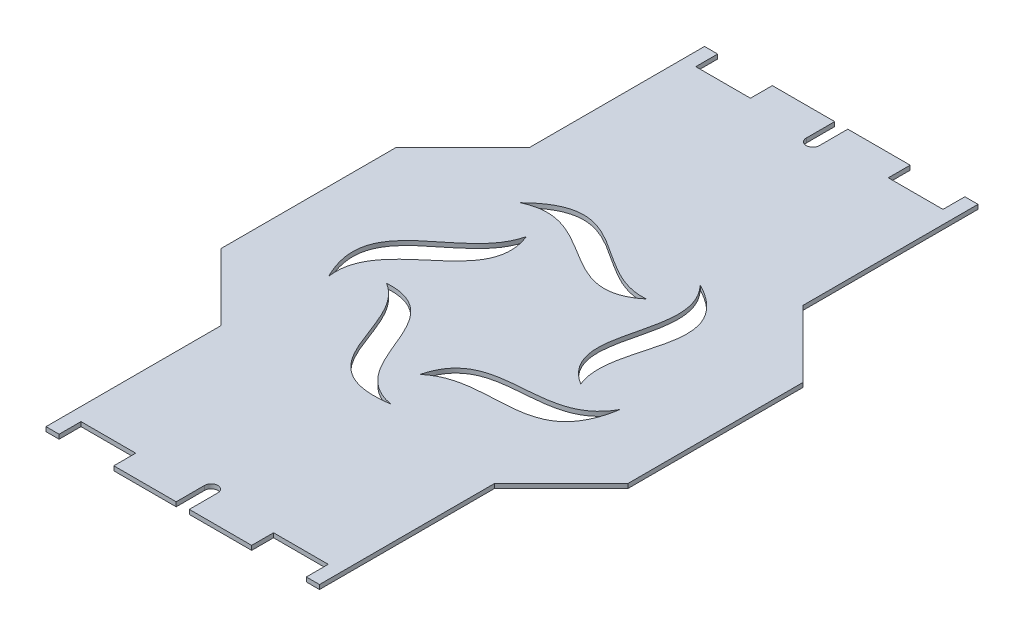
SolidWorks part; units mm, degrees
ref_plane "Front Plane" through (0, 0, 0) normal (0, 0, 1) x (1, 0, 0)
ref_plane "Top Plane" through (0, 0, 0) normal (0, 1, 0) x (1, 0, 0)
ref_plane "Right Plane" through (0, 0, 0) normal (1, 0, 0) x (0, 0, -1)
sketch "Sketch1" plane through (0, 0, 0) normal (0, 1, 0) x (1, 0, 0)
  line L0 (0, 0) -> (0, 150.5) construction
  line L1 (62.5, 150.5) -> (-62.5, 150.5)
  line L2 (-62.5, 150.5) -> (-62.5, 70.5)
  line L3 (-62.5, 70.5) -> (-93, 40)
  line L4 (-93, 40) -> (-93, -40)
  line L5 (0, 0) -> (-93, 0) construction
  line L6 (-62.5, -70.5) -> (-93, -40)
  line L7 (-62.5, -150.5) -> (-62.5, -70.5)
  line L8 (62.5, -150.5) -> (-62.5, -150.5)
  line L9 (62.5, -150.5) -> (62.5, -70.5)
  line L10 (62.5, -70.5) -> (93, -40)
  line L11 (93, 40) -> (93, -40)
  line L12 (62.5, 70.5) -> (93, 40)
  line L13 (62.5, 150.5) -> (62.5, 70.5)
  point P11 (0, -150.5)
  dimension "D1" = 80
  dimension "D2" = 40
extrude "Boss-Extrude1" add sketch "Sketch1" along normal blind 2
sketch "Sketch2" plane through (0, 2, 0) normal (0, 1, 0) x (1, 0, 0)
  line L0 (0, 0) -> (93, 0) construction
  line L1 (93, -40) -> (93, 40) construction
  line L2 (93, 0) -> (0, 0) construction
  line L3 (0, -150.5) -> (0, 150.5) construction
  line L4 (62.5, 150.5) -> (-62.5, 150.5) construction
  line L5 (-3, 150.5) -> (-3, 137.5)
  line L6 (3, 137.5) -> (3, 150.5)
  line L7 (3, 150.5) -> (-3, 150.5)
  line L8 (-3, 137.5) -> (-3, 150.5)
  line L9 (3, 150.5) -> (3, 137.5)
  line L10 (3, -150.5) -> (3, -137.5)
  line L11 (-3, -137.5) -> (-3, -150.5)
  line L12 (3, -150.5) -> (-3, -150.5)
  line L13 (3, -137.5) -> (3, -150.5)
  line L14 (-3, -150.5) -> (-3, -137.5)
  arc A0 (-3, 137.5) -> (3, 137.5) centre (0, 137.5) ccw
  arc A1 (-3, -137.5) -> (3, -137.5) centre (0, -137.5) cw
  point P12 (0, 0)
  line M9 (-62.5, -150.5) -> (62.5, -150.5)
  line M15 (62.5, 150.5) -> (-62.5, 150.5)
  dimension "D2" = 3
  dimension "D1" = 13
extrude "Cut-Extrude1" cut sketch "Sketch2" against normal blind 10 contours L5 A0 L6 M15 | A1 L11 L10 M9 region at (0, 2, -142.8073) region at (0, 2, 142.8073)
sketch "Sketch3" plane through (0, 2, 0) normal (0, 1, 0) x (1, 0, 0)
  circle A0 centre (0, 0) radius 75 construction
  spline S0 degree 3 poles (61.9353, -12.4807) (48.1881, -37.7648) (10.1523, -13.9307) (2.3401, -44.3064) knots 0 0 0 0 1 1 1 1
  spline S1 degree 3 poles (61.9353, -12.4807) (55.7621, -50.4582) (21.338, -28.075) (2.3401, -44.3064) knots 0 0 0 0 1 1 1 1
  spline S2 degree 3 poles (7.2692, -62.7607) (-21.0256, -57.4996) (-10.1116, -13.9602) (-41.4147, -15.917) knots 0 0 0 0 1 1 1 1
  spline S3 degree 3 poles (7.2692, -62.7607) (-30.7571, -68.6253) (-20.1071, -28.9693) (-41.4147, -15.917) knots 0 0 0 0 1 1 1 1
  spline S4 degree 3 poles (-57.4427, -26.3076) (-61.1826, 2.2281) (-16.4016, 5.3028) (-27.9358, 34.4691) knots 0 0 0 0 1 1 1 1
  spline S5 degree 3 poles (-57.4427, -26.3076) (-74.771, 8.0454) (-33.7649, 10.171) (-27.9358, 34.4691) knots 0 0 0 0 1 1 1 1
  spline S6 degree 3 poles (-42.7708, 46.5017) (-16.7874, 58.8767) (-0.0251, 17.2375) (24.1494, 37.2201) knots 0 0 0 0 1 1 1 1
  spline S7 degree 3 poles (-42.7708, 46.5017) (-15.4539, 73.5976) (-0.7608, 35.2553) (24.1494, 37.2201) knots 0 0 0 0 1 1 1 1
  spline S8 degree 3 poles (31.0089, 55.0473) (50.8075, 34.1597) (16.3861, 5.3506) (42.861, -11.4658) knots 0 0 0 0 1 1 1 1
  spline S9 degree 3 poles (31.0089, 55.0473) (65.22, 37.4405) (33.2947, 11.618) (42.861, -11.4658) knots 0 0 0 0 1 1 1 1
  point P35 (0, 0)
  dimension "D1" = 150
extrude "Cut-Extrude2" cut sketch "Sketch3" against normal blind 10
sketch "Sketch4" plane through (0, 2, 0) normal (0, 1, 0) x (1, 0, 0)
  line L0 (0, -150.5) -> (0, 150.5) construction
  line L1 (0, 150.5) -> (0, -150.5) construction
  line L2 (0, 0) -> (93, 0) construction
  line L3 (93, -40) -> (93, 40) construction
  line L4 (62.5, 150.5) -> (3, 150.5) construction
  line L5 (0, 150.5) -> (44, 150.5)
  line L6 (-31.5, 160.5) -> (-31.5, 140.5)
  line L7 (56.5, 160.5) -> (31.5, 160.5)
  line L8 (56.5, 160.5) -> (56.5, 140.5)
  line L9 (56.5, 140.5) -> (31.5, 140.5)
  line L10 (31.5, 160.5) -> (31.5, 140.5)
  line L11 (56.5, 160.5) -> (31.5, 140.5) construction
  line L12 (56.5, 140.5) -> (31.5, 160.5) construction
  line L13 (-56.5, 160.5) -> (-31.5, 160.5)
  line L14 (-56.5, 160.5) -> (-56.5, 140.5)
  line L15 (-56.5, 140.5) -> (-31.5, 140.5)
  line L16 (56.5, -140.5) -> (31.5, -160.5) construction
  line L17 (56.5, -160.5) -> (31.5, -140.5) construction
  line L18 (-56.5, -140.5) -> (-31.5, -140.5)
  line L19 (-56.5, -160.5) -> (-56.5, -140.5)
  line L20 (-56.5, -160.5) -> (-31.5, -160.5)
  line L21 (31.5, -160.5) -> (31.5, -140.5)
  line L22 (56.5, -140.5) -> (31.5, -140.5)
  line L23 (56.5, -160.5) -> (56.5, -140.5)
  line L24 (56.5, -160.5) -> (31.5, -160.5)
  line L25 (-31.5, -160.5) -> (-31.5, -140.5)
  line L26 (0, -150.5) -> (44, -150.5)
  line M23 (-3, 150.5) -> (-62.5, 150.5)
  line M29 (-62.5, -150.5) -> (-3, -150.5)
  line M33 (3, -150.5) -> (62.5, -150.5)
  line M39 (62.5, 150.5) -> (3, 150.5)
  dimension "D1" = 44
  dimension "D2" = 20
  dimension "D3" = 25
extrude "Cut-Extrude3" cut sketch "Sketch4" against normal blind 10 contours L7 L10 L8 M39 | L10 L9 L8 M39 | L14 L15 L6 M23 | L13 L14 L6 M23 | L20 L25 L19 M29 | L25 L18 L19 M29 | L23 L22 L21 M33 | L24 L23 L21 M33 region at (44, 2, -155.5) region at (44, 2, -145.5) region at (-44, 2, -155.5) region at (-44, 2, -145.5) region at (-44, 2, 145.5) region at (-44, 2, 155.5) region at (44, 2, 155.5) region at (44, 2, 145.5)
